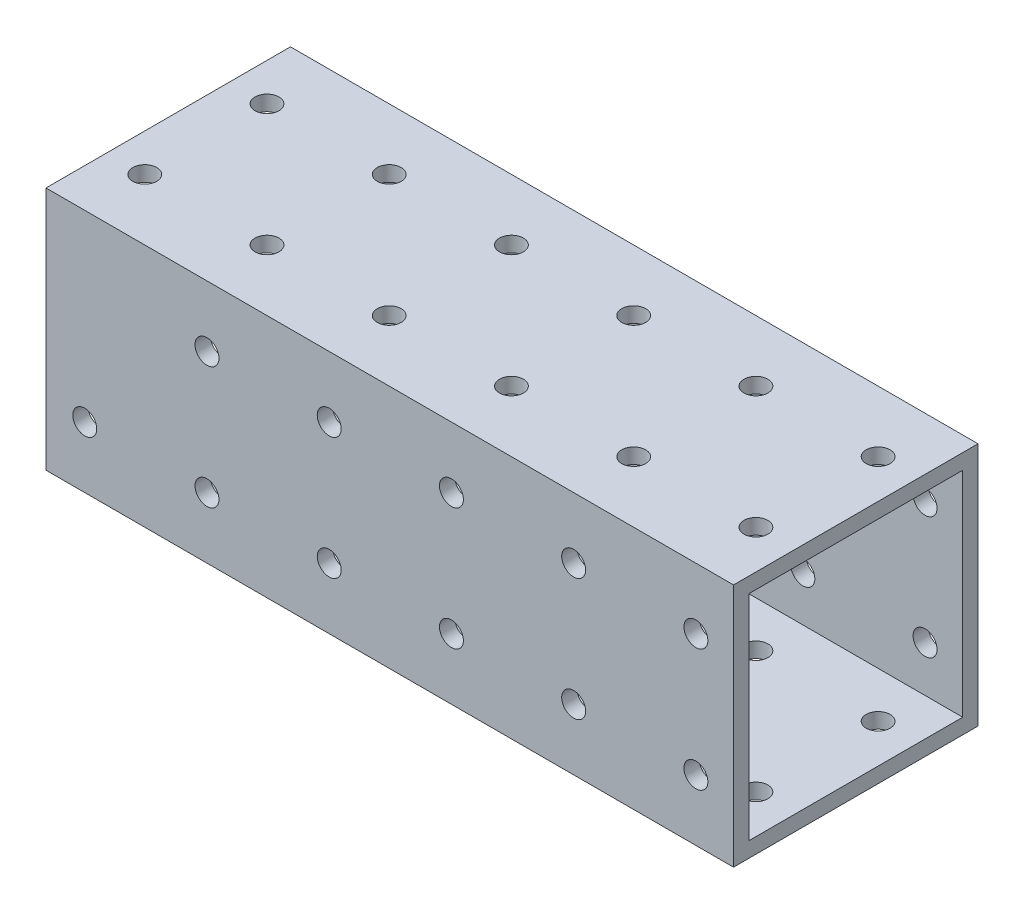
SolidWorks part; units mm, degrees
material "6061-T6 (SS)"
ref_plane "Front Plane" through (0, 0, 0) normal (0, 0, 1) x (1, 0, 0)
ref_plane "Top Plane" through (0, 0, 0) normal (0, 1, 0) x (1, 0, 0)
ref_plane "Right Plane" through (0, 0, 0) normal (1, 0, 0) x (0, 0, -1)
sketch "Sketch1" plane through (0, 0, 0) normal (1, 0, 0) x (0, 0, -1)
  line L1 (0, 0) -> (50.8, 0)
  line L2 (0, 0) -> (0, 50.8)
  line L3 (0, 50.8) -> (50.8, 50.8)
  line L4 (50.8, 0) -> (50.8, 50.8)
  dimension "D1" = 50.8
extrude "Boss-Extrude1" add sketch "Sketch1" along normal blind 142.875
shell "Shell1" thickness 3.175 removed face at (0, 25.4, -25.4) removed face at (142.875, 25.4, -25.4)
sketch "Sketch2" plane through (0, 0, -50.8) normal (0, 0, -1) x (-1, 0, 0)
  line L1 (-142.875, 0) -> (0, 0) construction
  line L2 (0, 0) -> (0, 50.8) construction
  circle A22 centre (-8.0518, 38.1) radius 2.4892 construction
  circle A23 centre (-33.4518, 38.1) radius 2.4892
  circle A24 centre (-58.8518, 38.1) radius 2.4892
  circle A25 centre (-84.2518, 38.1) radius 2.4892
  circle A26 centre (-109.6518, 38.1) radius 2.4892
  circle A27 centre (-135.0518, 38.1) radius 2.4892
  circle A28 centre (-33.4518, 12.7) radius 2.4892
  circle A29 centre (-58.8518, 12.7) radius 2.4892
  circle A30 centre (-84.2518, 12.7) radius 2.4892
  circle A31 centre (-109.6518, 12.7) radius 2.4892
  circle A32 centre (-135.0518, 12.7) radius 2.4892
  circle A33 centre (-8.0518, 12.7) radius 2.4892
  dimension "D5" = 2
  dimension "D3" = 38.1
  dimension "D1" = 4.9784
  dimension "D2" = 135.0518
  dimension "D4" = 6
  dimension "D6" = 25.4
  dimension "D7" = 25.4
extrude "Cut-Extrude1" cut sketch "Sketch2" against normal through all contours A31 | A32 | A28 | A26 | A25 | A30 | A24 | A29 | A23 | A22 | A33 | A27 region at (33.4518, 38.1, -50.8) region at (58.8518, 38.1, -50.8) region at (84.2518, 38.1, -50.8) region at (109.6518, 38.1, -50.8) region at (135.0518, 38.1, -50.8) region at (33.4518, 12.7, -50.8) region at (58.8518, 12.7, -50.8) region at (84.2518, 12.7, -50.8) region at (109.6518, 12.7, -50.8) region at (135.0518, 12.7, -50.8) region at (8.0518, 12.7, -50.8)
sketch "Sketch3" plane through (0, 0, 0) normal (0, -1, 0) x (1, 0, 0)
  line L0 (142.875, 0) -> (142.875, -50.8) construction
  line L1 (142.875, -50.8) -> (0, -50.8) construction
  circle A2 centre (134.8232, -12.7) radius 2.4892
  circle A3 centre (109.4232, -12.7) radius 2.4892
  circle A4 centre (84.0232, -12.7) radius 2.4892
  circle A5 centre (58.6232, -12.7) radius 2.4892
  circle A6 centre (33.2232, -12.7) radius 2.4892
  circle A7 centre (7.8232, -12.7) radius 2.4892
  circle A8 centre (109.4232, -38.1) radius 2.4892
  circle A9 centre (84.0232, -38.1) radius 2.4892
  circle A10 centre (58.6232, -38.1) radius 2.4892
  circle A11 centre (33.2232, -38.1) radius 2.4892
  circle A12 centre (7.8232, -38.1) radius 2.4892
  circle A13 centre (134.8232, -38.1) radius 2.4892
  dimension "D1" = 4.9784
  dimension "D2" = 8.0518
  dimension "D3" = 38.1
  dimension "D6" = 25.4
  dimension "D7" = 25.4
  dimension "D4" = 6
  dimension "D5" = 2
extrude "Cut-Extrude2" cut sketch "Sketch3" against normal through all
